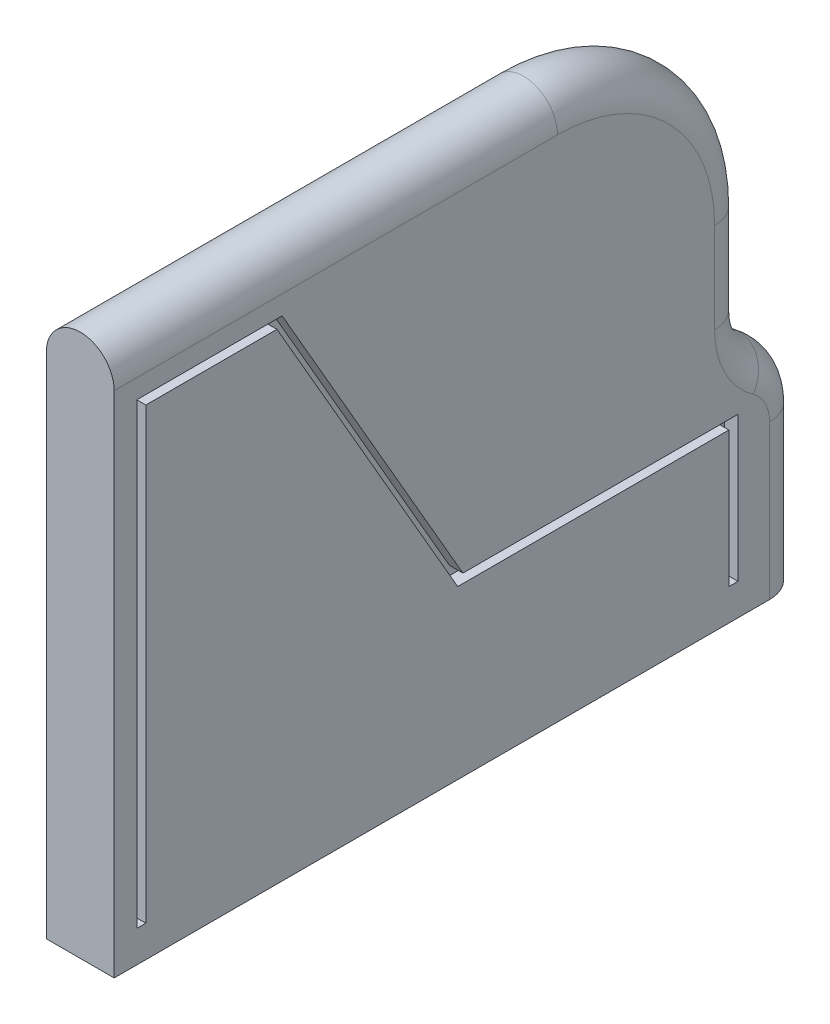
SolidWorks part; units mm, degrees
material "Mahogany"
ref_plane "Front Plane" through (0, 0, 0) normal (0, 0, 1) x (1, 0, 0)
ref_plane "Top Plane" through (0, 0, 0) normal (0, 1, 0) x (1, 0, 0)
ref_plane "Right Plane" through (0, 0, 0) normal (1, 0, 0) x (0, 0, -1)
sketch "Sketch1" plane through (0, 0, 0) normal (1, 0, 0) x (0, 0, -1)
  line L0 (105.1766, -44.2663) -> (105.1766, -78.3086)
  line L1 (-47.3234, -78.3086) -> (105.1766, -78.3086)
  line L2 (-47.3234, -78.3086) -> (-47.3234, 41.6914)
  line L4 (93.0061, -20.5453) -> (93.0061, -0.568)
  line L5 (-47.3234, 41.6914) -> (50.7467, 41.6914)
  arc A0 (93.0061, -0.568) -> (50.7467, 41.6914) centre (50.7467, -0.568) ccw
  arc A1 (93.0061, -20.5453) -> (98.41, -31.0778) centre (105.9723, -20.5453) ccw
  arc A2 (98.41, -31.0778) -> (105.1766, -44.2663) centre (88.9408, -44.2663) cw
  point P0 (9.7933, -6.725)
  dimension "D1" = 152.5
  dimension "D2" = 120
extrude "Boss-Extrude1" add sketch "Sketch1" along normal blind 15
sketch "Sketch3" plane through (15, 0, 0) normal (1, 0, 0) x (0, 0, -1)
  line L0 (90.6766, -71.3086) -> (90.6766, -39.3086)
  line L1 (90.6766, -39.3086) -> (29.8313, -39.3086)
  line L2 (29.8313, -39.3086) -> (-10.1687, 29.9735)
  line L3 (-10.1687, 29.9735) -> (-42.3234, 29.9735)
  line L4 (-42.3234, 29.9735) -> (-42.3234, -71.3086)
  line L5 (-42.3234, -71.3086) -> (-40.3234, -71.3086)
  line L6 (-40.3234, -71.3086) -> (-40.3234, 27.9735)
  line L7 (-40.3234, 27.9735) -> (-11.3234, 27.9735)
  line L8 (-11.3234, 27.9735) -> (28.6766, -41.3086)
  line L9 (28.6766, -41.3086) -> (88.6766, -41.3086)
  line L10 (88.6766, -41.3086) -> (88.6766, -71.3086)
  line L11 (88.6766, -71.3086) -> (90.6766, -71.3086)
  line L12 (-47.3234, -78.3086) -> (105.1766, -78.3086) construction
  line L15 (-47.3234, 41.6914) -> (-47.3234, -78.3086) construction
  dimension "D1" = 2
  dimension "D2" = 2
  dimension "D3" = 2
  dimension "D4" = 2
  dimension "D5" = 2
  dimension "D6" = 30
  dimension "D7" = 60
  dimension "D8" = 60
  dimension "D9" = 80
  dimension "D10" = 29
  dimension "D11" = 5
  dimension "D12" = 7
extrude "Cut-Extrude4" cut sketch "Sketch3" against normal blind 3
fillet "Fillet1" 12 edges at (15, -26.4643, -94.4359) (15, -10.5567, -93.0061) (15, 29.3139, -80.6286) (15, 41.6914, -1.7116) (15, -61.2874, -105.1766) (15, -36.8548, -103.3862) (0, -26.4643, -94.4359) (0, -10.5567, -93.0061) (0, 29.3139, -80.6286) (0, 41.6914, -1.7116) (0, -61.2874, -105.1766) (0, -36.8548, -103.3862) type full round first side face at (15, -27.5479, -19.2023) second side face at (0, -20.0969, -57.4935) middle face at (7.5, 41.6914, -1.7116) middle face at (7.5, 24.9378, -76.2525) middle face at (7.5, -10.5567, -93.0061) middle face at (7.5, -26.1379, -95.072) middle face at (7.5, -37.2634, -102.5897) middle face at (7.5, -61.2874, -105.1766)
